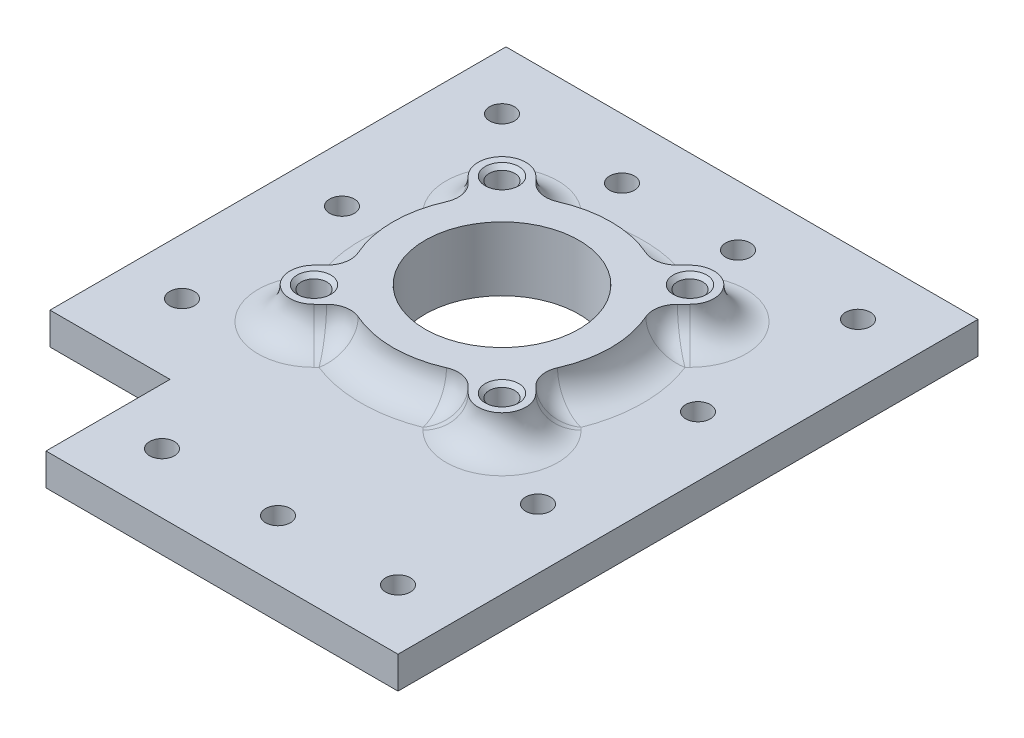
SolidWorks part; units mm, degrees
material "PET"
ref_plane "Front Plane" through (0, 0, 0) normal (0, 0, 1) x (1, 0, 0)
ref_plane "Top Plane" through (0, 0, 0) normal (0, 1, 0) x (1, 0, 0)
ref_plane "Right Plane" through (0, 0, 0) normal (1, 0, 0) x (0, 0, -1)
sketch "Sketch1" plane through (0, 0, 0) normal (0, 1, 0) x (1, 0, 0)
  line L1 (-59, 60) -> (59, 60)
  line L2 (-59, 60) -> (-59, -85)
  line L3 (-59, -85) -> (59, -85)
  line L4 (59, 60) -> (59, -85)
  circle A0 centre (0, 0) radius 19.25
  point P0 (0, 0)
  dimension "D4" = 38.5
  dimension "D1" = 118
  dimension "D2" = 145
  dimension "D3" = 59
  dimension "D5" = 60
extrude "Boss-Extrude1" add sketch "Sketch1" along normal blind 8
sketch "Sketch5" plane through (0, 8, 0) normal (0, 1, 0) x (1, 0, 0)
  circle A0 centre (0, 0) radius 19.25
  circle A1 centre (0, 0) radius 27.25
  dimension "D1" = 38.5
  dimension "D2" = 8
extrude "Boss-Extrude2" add sketch "Sketch5" along normal blind 8
sketch "Sketch9" plane through (0, 8, 0) normal (0, 1, 0) x (1, 0, 0)
  line L0 (17.6998, 26.1624) -> (19.2687, 27.7313)
  line L1 (-23.5, -23.5) -> (23.5, -23.5) construction
  line L2 (-23.5, -23.5) -> (-23.5, 23.5) construction
  line L3 (-23.5, 23.5) -> (23.5, 23.5) construction
  line L4 (23.5, -23.5) -> (23.5, 23.5) construction
  line L5 (-23.5, -23.5) -> (23.5, 23.5) construction
  line L6 (-23.5, 23.5) -> (23.5, -23.5) construction
  line L7 (19.2687, -27.7313) -> (17.6998, -26.1624)
  line L8 (27.7313, -19.2687) -> (26.1624, -17.6998)
  line L9 (-27.7313, -19.2687) -> (-26.1624, -17.6998)
  line L10 (-19.2687, -27.7313) -> (-17.6998, -26.1624)
  line L11 (-26.1624, 17.6998) -> (-27.7313, 19.2687)
  line L12 (-17.6998, 26.1624) -> (-19.2687, 27.7313)
  line L13 (26.1624, 17.6998) -> (27.7313, 19.2687)
  circle A1 centre (-23.5, -23.5) radius 5.984
  circle A2 centre (-23.5, 23.5) radius 5.984
  circle A3 centre (23.5, 23.5) radius 5.984
  circle A4 centre (23.5, -23.5) radius 5.984
  arc A5 (-24.9184, -11.0288) -> (-11.0288, -24.9184) centre (0, 0) ccw
  arc A6 (-11.0288, 24.9184) -> (-24.9184, 11.0288) centre (0, 0) ccw
  arc A7 (24.9184, 11.0288) -> (11.0288, 24.9184) centre (0, 0) ccw
  arc A8 (26.1624, -17.6998) -> (24.9184, -11.0288) centre (30.4051, -13.4571) cw
  arc A9 (17.6998, -26.1624) -> (11.0288, -24.9184) centre (13.4571, -30.4051) ccw
  arc A10 (-26.1624, -17.6998) -> (-24.9184, -11.0288) centre (-30.4051, -13.4571) ccw
  arc A11 (-17.6998, -26.1624) -> (-11.0288, -24.9184) centre (-13.4571, -30.4051) cw
  arc A12 (26.1624, 17.6998) -> (24.9184, 11.0288) centre (30.4051, 13.4571) ccw
  arc A13 (17.6998, 26.1624) -> (11.0288, 24.9184) centre (13.4571, 30.4051) cw
  arc A14 (-17.6998, 26.1624) -> (-11.0288, 24.9184) centre (-13.4571, 30.4051) ccw
  arc A15 (-26.1624, 17.6998) -> (-24.9184, 11.0288) centre (-30.4051, 13.4571) cw
  arc A16 (11.0288, -24.9184) -> (24.9184, -11.0288) centre (0, 0) ccw
  point P0 (0, 0)
  point P30 (23.0297, -14.567)
  point P41 (14.567, 23.0297)
  point P46 (-23.0297, 14.567)
  circle M29 centre (0, 0) radius 27.25
  dimension "D2" = 54.5
  dimension "D3" = 6
  dimension "D1" = 47
sketch "Sketch12" plane through (0, 8, 0) normal (0, 1, 0) x (1, 0, 0)
  line L1 (-59, -85) -> (-29, -85)
  line L2 (-59, -85) -> (-59, -54)
  line L3 (-59, -54) -> (-29, -54)
  line L4 (-29, -85) -> (-29, -54)
  dimension "D1" = 30
  dimension "D2" = 31
extrude "Cut-Extrude1" cut sketch "Sketch12" against normal through all
sketch "Sketch14" plane through (0, 8, 0) normal (0, 1, 0) x (1, 0, 0)
  line L0 (-59, 60) -> (-59, -54) construction
  line L1 (44, 45) -> (-45, 45) construction
  line L2 (44, 45) -> (44, -70) construction
  line L3 (44, -70) -> (-45, -70) construction
  line L4 (-45, 45) -> (-45, -70) construction
  line L5 (59, 60) -> (-59, 60) construction
  line L6 (59, -85) -> (59, 60) construction
  line L7 (-29, -85) -> (59, -85) construction
  point P0 (0, 0)
  point P10 (-45, 5)
  point P11 (-45, -35)
  point P12 (-15, 45)
  point P13 (14, 45)
  point P14 (-15, -70)
  point P15 (14, -70)
  point P18 (0, 60)
  point P21 (44, 5)
  point P22 (44, -35)
  dimension "D3" = 40
  dimension "D4" = 40
  dimension "D5" = 30
  dimension "D6" = 30
  dimension "D7" = 30
  dimension "D8" = 30
  dimension "D9" = 15
  dimension "D10" = 15
  dimension "D1" = 14
  dimension "D2" = 15
hole_wizard "Ø6.2 (6.2) Diameter Hole2" positions "Sketch15" profile "Sketch16" hole size "Ø6.2" standard "ANSI Metric" end condition through all
sketch "Sketch15" plane through (0, 8, 0) normal (0, 1, 0) x (1, 0, 0)
  point P0 (-45, -35)
  point P3 (-45, 5)
  point P6 (-45, 45)
  point P9 (-15, 45)
  point P12 (14, 45)
  point P15 (44, 45)
  point P18 (-15, -70)
  point P21 (14, -70)
  point P24 (44, -70)
  point P27 (44, 5)
  point P29 (44, -35)
sketch "Sketch16" plane through (-45, 8, 35) normal (1, 0, 0) x (0, 0, 1)
  line L0 (0, 0) -> (0, 8)
  line L1 (0, 8) -> (3.1, 8)
  line L2 (3.1, 8) -> (3.1, 0)
  line L5 (3.1, 0) -> (0, 0)
  line L11 (0, -6.35) -> (0, 107.95) construction
  dimension "Thru Hole Dia." = 6.2
  dimension "Thru Hole Depth" = 8
extrude "Boss-Extrude6" add sketch "Sketch9" along normal blind 8 contours L11 A15 A2 M29 | A14 L12 A2 M29 | A2 | A12 L13 A3 M29 | L0 A13 A3 M29 | A3 | L10 A11 A1 M29 | A10 L9 A1 M29 | A1 | A9 L7 A4 M29 | L8 A8 A4 M29 | A4 region at (16.1538, 8, -23.5548) region at (23.5, 8, -23.5) region at (23.5548, 8, -16.1538) region at (-16.1538, 8, -23.5548) region at (-23.5548, 8, -16.1538) region at (-23.5, 8, -23.5) region at (23.5548, 8, 16.1538) region at (-23.5548, 8, 16.1538) region at (23.5, 8, 23.5) region at (16.1538, 8, 23.5548) region at (-16.1538, 8, 23.5548) region at (-23.5, 8, 23.5)
hole_wizard "Ø6.4 (6.4) Diameter Hole1" positions "Sketch19" profile "Sketch20" hole size "Ø6.4" standard "ANSI Metric" end condition through all
sketch "Sketch19" plane through (0, 16, 0) normal (0, 1, 0) x (1, 0, 0)
  point P0 (-23.5, -23.5)
  point P3 (23.5, -23.5)
  point P6 (23.5, 23.5)
  point P9 (-23.5, 23.5)
sketch "Sketch20" plane through (-23.5, 16, 23.5) normal (1, 0, 0) x (0, 0, 1)
  line L0 (0, 0) -> (0, 16)
  line L1 (0, 16) -> (3.2, 16)
  line L2 (3.2, 16) -> (3.2, 0)
  line L5 (3.2, 0) -> (0, 0)
  line L11 (0, -6.35) -> (0, 107.95) construction
  dimension "Thru Hole Dia." = 6.4
  dimension "Thru Hole Depth" = 16
fillet "Fillet1" radius 8 24 edges at (26.9469, 8, -18.4842) (27.7313, 8, -27.7313) (18.4842, 8, -26.9469) (14.557, 8, -24.5068) (0, 8, -27.25) (-14.557, 8, -24.5068) (-18.4842, 8, -26.9469) (-27.7313, 8, -27.7313) (-26.9469, 8, -18.4842) (-24.5068, 8, -14.557) (-27.25, 8, 0) (-24.5068, 8, 14.557) (-26.9469, 8, 18.4842) (-27.7313, 8, 27.7313) (-18.4842, 8, 26.9469) (-14.557, 8, 24.5068) (0, 8, 27.25) (14.557, 8, 24.5068) (18.4842, 8, 26.9469) (27.7313, 8, 27.7313) (26.9469, 8, 18.4842) (24.5068, 8, 14.557) (27.25, 8, 0) (24.5068, 8, -14.557)
chamfer "Chamfer3" distance 1 angle 45 4 edges at (23.5, 16, -20.3) (23.5, 16, 26.7) (-23.5, 16, 26.7) (-23.5, 16, -20.3)
